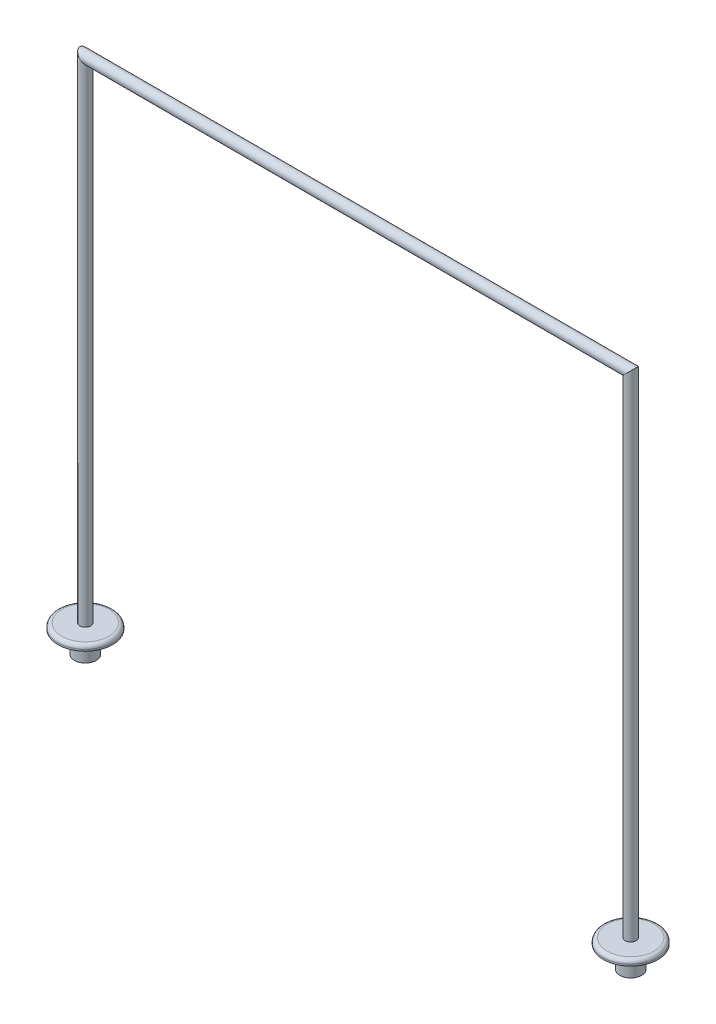
SolidWorks part; units mm, degrees
ref_plane "Front Plane" through (0, 0, 0) normal (0, 0, 1) x (1, 0, 0)
ref_plane "Top Plane" through (0, 0, 0) normal (0, 1, 0) x (1, 0, 0)
ref_plane "Right Plane" through (0, 0, 0) normal (1, 0, 0) x (0, 0, -1)
sketch "Sketch3" plane through (0, 0, 0) normal (0, 0, 1) x (1, 0, 0)
  line L0 (0, 0) -> (0, 90)
  line L3 (0, 90) -> (100, 90)
  line L4 (100, 90) -> (100, 0)
  dimension "D1" = 100
  dimension "D2" = 90
ref_plane "Plane3" through (0, 0, 0) normal (1, 0, 0) x (0, 1, 0)
sketch "Sketch4" plane through (0, 0, 0) normal (1, 0, 0) x (0, 1, 0)
  line L0 (0, 0) -> (0, -4.3)
  line L1 (-0.7, -5) -> (-1, -5)
  line L2 (-1, -5) -> (-1, 0)
  line L3 (-1, 0) -> (0, 0)
  line L5 (-1, 0) -> (-5, 0)
  line L6 (-1, 0) -> (-1, -2)
  line L7 (-1, -2) -> (-5, -2)
  line L8 (-5, 0) -> (-5, -2)
  arc A0 (0, -4.3) -> (-0.7, -5) centre (-0.7, -4.3) cw
  point P7 (0, -5)
  point P11 (-3, 0)
  dimension "D3" = 0.7
  dimension "D1" = 5
  dimension "D2" = 1
  dimension "D4" = 2
  dimension "D5" = 4
sketch "Sketch5" plane through (0, 0, 0) normal (0, 1, 0) x (1, 0, 0)
  circle A0 centre (0, 0) radius 1
  dimension "D1" = 2
sweep "Sweep1" add profiles "Sketch5" path "Sketch3"
ref_axis "Axis1" through (0, 0, 0) along (0, 1, 0)
ref_axis "Axis2" through (100, 91, 0) along (0, -1, 0)
ref_axis "Axis3" through (-1, 90, 0) along (1, 0, 0)
revolve "Revolve1" add sketch "Sketch4" angle 360 about axis through (0, 0, 0) along (0, 1, 0)
sketch "Sketch6" plane through (0, 0, 0) normal (0, 0, 1) x (1, 0, 0)
  line L0 (50, 90) -> (50, 80)
  line L1 (-1, 90) -> (101, 90) construction
  line L2 (0, -55) -> (0, 55) construction
  dimension "D1" = 50
  dimension "D2" = 10
ref_plane "Plane6" through (50, 0, 0) normal (1, 0, 0) x (0, 0, -1)
mirror "Mirror1" about plane through (50, 0, 0) normal (1, 0, 0) of "Revolve1"
